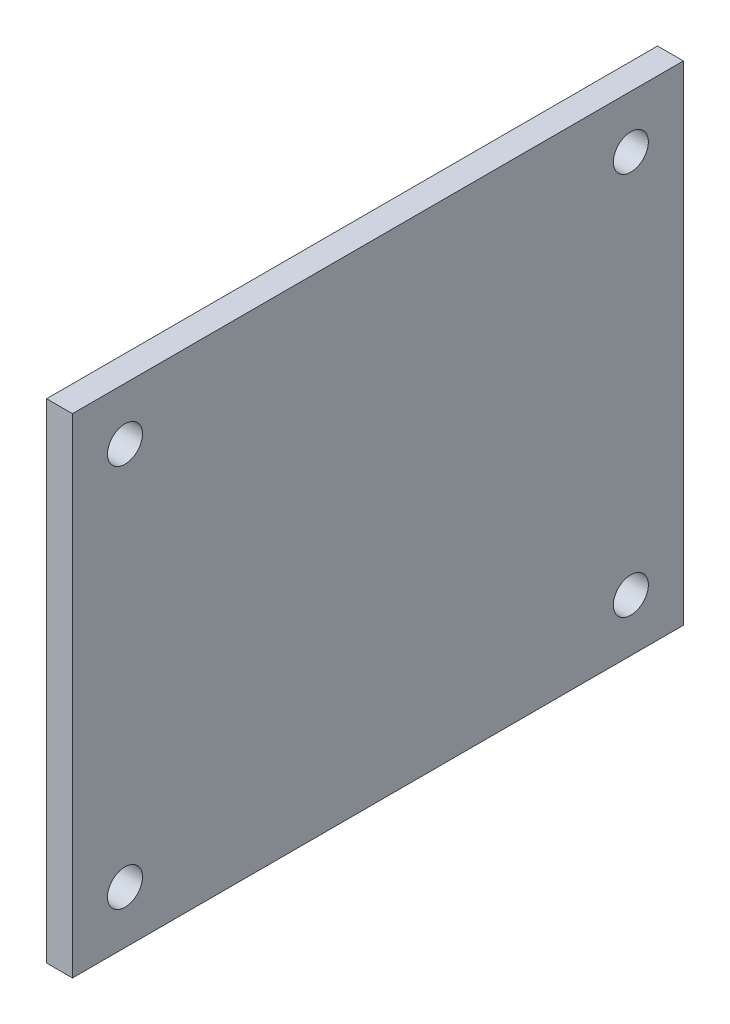
SolidWorks part; units mm, degrees
ref_plane "Front Plane" through (0, 0, 0) normal (0, 0, 1) x (1, 0, 0)
ref_plane "Top Plane" through (0, 0, 0) normal (0, 1, 0) x (1, 0, 0)
ref_plane "Right Plane" through (0, 0, 0) normal (1, 0, 0) x (0, 0, -1)
sketch "Sketch1" plane through (0, 0, 0) normal (1, 0, 0) x (0, 0, -1)
  line L1 (-37.5, -30) -> (37.5, -30)
  line L2 (-37.5, -30) -> (-37.5, 30)
  line L3 (-37.5, 30) -> (37.5, 30)
  line L4 (37.5, -30) -> (37.5, 30)
  line L5 (-37.5, -30) -> (37.5, 30) construction
  line L6 (-37.5, 30) -> (37.5, -30) construction
  point P0 (0, 0)
  dimension "D1" = 75
  dimension "D2" = 60
extrude "Boss-Extrude1" add sketch "Sketch1" along normal blind 1.5875 and the other way blind 1.5875
sketch "Sketch2" plane through (0, 0, 0) normal (1, 0, 0) x (0, 0, -1)
  line L0 (-37.5, 30) -> (-31.05, 30) construction
  line L1 (37.5, 30) -> (-37.5, 30) construction
  line L2 (-31.05, 30) -> (-31.05, 23.55) construction
  line L3 (0, 55) -> (0, -55) construction
  line L4 (55, 0) -> (-55, 0) construction
  circle A0 centre (-31.05, 23.55) radius 2.15
  circle A1 centre (31.05, 23.55) radius 2.15
  circle A2 centre (31.05, -23.55) radius 2.15
  circle A3 centre (-31.05, -23.55) radius 2.15
  dimension "D3" = 4.3
  dimension "D1" = 6.45
  dimension "D2" = 6.45
extrude "Cut-Extrude1" cut sketch "Sketch2" against normal through all both and the other way through all
